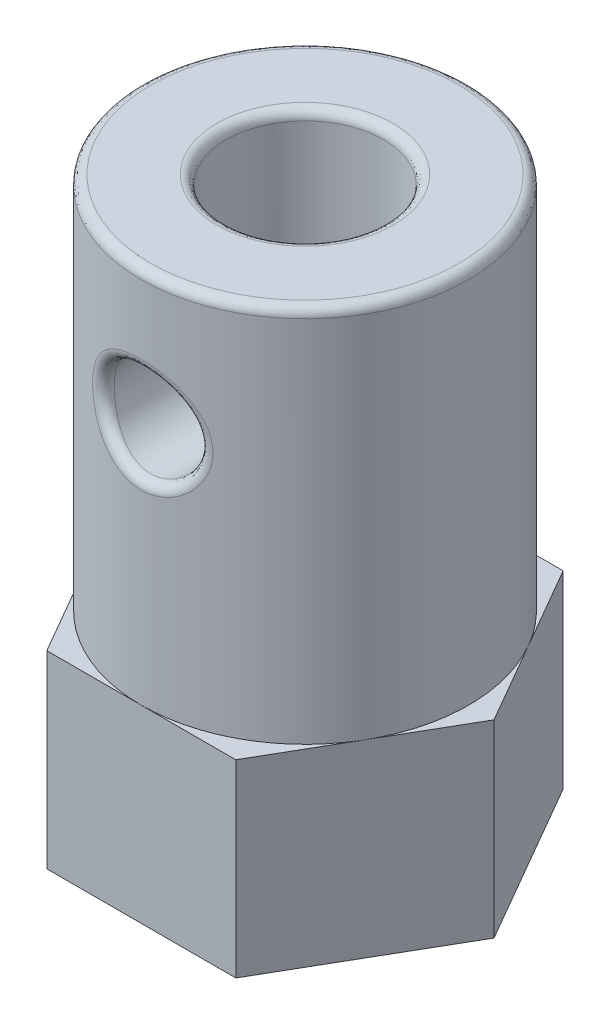
SolidWorks part; units mm, degrees
ref_plane "Front Plane" through (0, 0, 0) normal (0, 0, 1) x (1, 0, 0)
ref_plane "Top Plane" through (0, 0, 0) normal (0, 1, 0) x (1, 0, 0)
ref_plane "Right Plane" through (0, 0, 0) normal (1, 0, 0) x (0, 0, -1)
sketch "Sketch1" plane through (0, 0, 0) normal (0, 1, 0) x (1, 0, 0)
  line L1 (-3, 5.1962) -> (-6, 0)
  line L2 (-6, 0) -> (-3, -5.1962)
  line L3 (-3, -5.1962) -> (3, -5.1962)
  line L4 (3, -5.1962) -> (6, 0)
  line L5 (6, 0) -> (3, 5.1962)
  line L6 (3, 5.1962) -> (-3, 5.1962)
  circle A0 centre (0, 0) radius 6
  circle A1 centre (0, 0) radius 5.1962 construction
  circle A2 centre (0, 0) radius 2
  dimension "D1" = 12
  dimension "D2" = 4
extrude "Boss-Extrude2" add sketch "Sketch1" along normal blind 6 contours L3 L4 L5 L6 L1 L2
sketch "Sketch3" plane through (0, 6, 0) normal (0, 1, 0) x (1, 0, 0)
  circle A0 centre (0, 0) radius 5.1962
  circle A1 centre (0, 0) radius 2.5
  dimension "D1" = 10.3923
  dimension "D2" = 5
extrude "Boss-Extrude4" add sketch "Sketch3" along normal blind 12
extrude "Cut-Extrude2" cut sketch "Sketch1<4>" along normal up to next contours A2
sketch "Sketch1<4>" plane through (0, 0, 0) normal (0, 1, 0) x (1, 0, 0) same geometry as "Sketch1"
ref_plane "Plane1" through (0, 0, 5.1962) normal (0, 0, 1) x (1, 0, 0)
sketch "Sketch4" plane through (0, 0, 5.1962) normal (0, 0, 1) x (1, 0, 0)
  circle A0 centre (0, 13.7145) radius 1.5
  dimension "D1" = 3
extrude "Cut-Extrude3" cut sketch "Sketch4" against normal up to next
fillet "Fillet3" radius 0.3 4 edges at (0, 0, 2) (-1.4741, 13.437, 4.9827) (0, 18, 2.5) (0, 18, 5.1962) first distance on face at (0, 6, 2) first distance on face at (-1.4741, 13.437, 4.9827) first distance on face at (0, 18, 5.1962)
